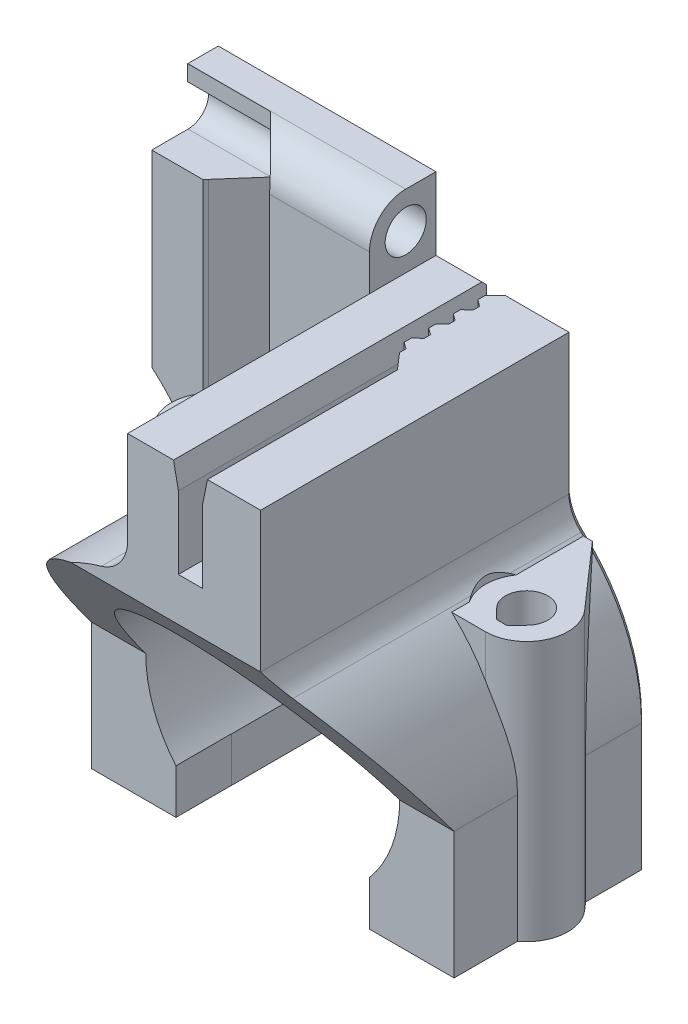
SolidWorks part; units mm, degrees
material "Custom Plastic"
ref_plane "Front Plane" through (0, 0, 0) normal (0, 0, 1) x (1, 0, 0)
ref_plane "Top Plane" through (0, 0, 0) normal (0, 1, 0) x (1, 0, 0)
ref_plane "Right Plane" through (0, 0, 0) normal (1, 0, 0) x (0, 0, -1)
sketch "Sketch1" plane through (0, 0, 0) normal (0, 0, 1) x (1, 0, 0)
  line L0 (-23.622, -10.5) -> (30.4823, -10.5) construction
  line L1 (-23.622, -16.5) -> (30.4823, -16.5) construction
  line L2 (8, -6.8007) -> (8, -10.5)
  line L3 (8, -10.5) -> (15, -10.5)
  line L4 (-15, -10.5) -> (-8, -10.5)
  line L5 (-8, -6.8007) -> (-8, -10.5)
  line L6 (15, 0) -> (15, -10.5)
  line L7 (-2, 25) -> (9, 25)
  line L9 (9, 25) -> (9, 13.4164)
  line L10 (-2, 25) -> (-2, 17.2916)
  line L12 (-15, -10.5) -> (-15, 0)
  arc A0 (-4.1667, 14.4097) -> (-2, 17.2916) centre (-5, 17.2916) ccw
  arc A1 (15, 0) -> (10, 11.1803) centre (0, 0) ccw
  arc A2 (10, 11.1803) -> (9, 13.4164) centre (12, 13.4164) cw
  arc A4 (8, -6.8007) -> (-8, -6.8007) centre (0, 0) ccw
  arc A5 (-4.1667, 14.4097) -> (-15, 0) centre (0, 0) ccw
  dimension "D1" = 16
  dimension "D4" = 25
  dimension "D5" = 2
  dimension "D6" = 21
  dimension "D7" = 4.5
  dimension "D3" = 3
  dimension "D8" = 3
  dimension "D9" = 9
  dimension "D2" = 6
extrude "Boss-Extrude1" add sketch "Sketch1" along normal blind 26
sketch "Sketch4" plane through (0, -10.5, 0) normal (0, -1, 0) x (1, 0, 0)
  line L0 (10.939, 0.5) -> (7.9931, 0.5)
  line L3 (13, 11.4) -> (7.9931, 11.4)
  line L4 (7.9931, 11.4) -> (7.9931, 0.5)
  line L5 (10.939, 0.5) -> (15.5548, 5.7566)
  arc A1 (15.5548, 5.7566) -> (13, 11.4) centre (13, 8) ccw
  dimension "D1" = 3.4
  dimension "D2" = 13
  dimension "D4" = 8
extrude "Boss-Extrude2" add sketch "Sketch4" against normal blind 21.5
sketch "Sketch2" plane through (0, -10.5, 0) normal (0, -1, 0) x (1, 0, 0)
  line L0 (13, 16) -> (13, 0) construction
  circle A0 centre (13, 8) radius 1.75
  arc A3 (15.5548, 5.7566) -> (15, 10.7495) centre (13, 8) ccw construction
  dimension "D1" = 3.5
extrude "Cut-Extrude1" cut sketch "Sketch2" against normal through all
mirror "Mirror1" about plane through (0, 0, 0) normal (1, 0, 0) of "Boss-Extrude2", "Cut-Extrude1"
sketch "Sketch5" plane through (0, -10.5, 0) normal (0, -1, 0) x (1, 0, 0)
  line L0 (-13, 8) -> (-11.7626, 9.2374)
  line L1 (-11.7626, 9.2374) -> (-12.5951, 10.07)
  line L2 (-12.5951, 10.07) -> (-13.4049, 10.07)
  line L3 (-13.4049, 10.07) -> (-14.2374, 9.2374)
  line L4 (-14.2374, 9.2374) -> (-13, 8)
  line L5 (13, 8) -> (14.2374, 9.2374)
  line L6 (14.2374, 9.2374) -> (13.4049, 10.07)
  line L7 (12.5951, 10.07) -> (11.7626, 9.2374)
  line L8 (11.7626, 9.2374) -> (13, 8)
  line L9 (12.5951, 10.07) -> (13.4049, 10.07)
  circle A0 centre (-13, 8) radius 1.75 construction
  circle A1 centre (13, 8) radius 1.75 construction
  point P0 (-13, 9.75)
  point P4 (13, 9.75)
  dimension "D1" = 0.32
  dimension "D2" = 0.32
extrude "Cut-Extrude3" cut sketch "Sketch5" against normal through all
sketch "Sketch7" plane through (0, 25, 0) normal (0, 1, 0) x (1, 0, 0)
  line L0 (3.2, -3.116) -> (3.2, -10.7303) construction
  line L1 (3.45, -2.334) -> (2.9, -1.934)
  line L2 (2.9, -1.934) -> (2.9, -1.334)
  line L19 (4.2, -9.8281) -> (4.2, -26)
  line L22 (3.45, -8.962) -> (4.2, -9.8281)
  line L23 (2.9, -1.334) -> (4.2, 0)
  line L24 (3.45, -8.43) -> (3.45, -8.962)
  line L25 (3.45, -6.398) -> (3.45, -6.93)
  line L26 (3.45, -4.366) -> (3.45, -4.898)
  line L27 (2.9, -8.03) -> (3.45, -8.43)
  line L28 (2.9, -7.43) -> (2.9, -8.03)
  line L29 (3.45, -6.93) -> (2.9, -7.43)
  line L30 (2.9, -5.998) -> (3.45, -6.398)
  line L31 (2.9, -5.398) -> (2.9, -5.998)
  line L32 (3.45, -4.898) -> (2.9, -5.398)
  line L33 (2.9, -3.966) -> (3.45, -4.366)
  line L34 (2.9, -3.366) -> (2.9, -3.966)
  line L35 (3.45, -2.866) -> (2.9, -3.366)
  line L36 (2.2, 0) -> (2.2, -26)
  line L37 (4.2, -26) -> (2.2, -26)
  line L38 (3.45, -2.334) -> (3.45, -2.866)
  line L39 (4.2, 0) -> (2.2, 0)
  point P0 (3.2, -3.116)
  dimension "D1" = 0.6
  dimension "D2" = 0.55
  dimension "D3" = 2.032
  dimension "D4" = 1.25
  dimension "D5" = 2
  dimension "D8" = 3.2
extrude "Cut-Extrude4" cut sketch "Sketch7" against normal blind 8
sketch "Sketch13" plane through (0, 0, 0) normal (0, 0, -1) x (-1, 0, 0)
  line L0 (2, 17.2916) -> (2, 31)
  line L1 (2, 31) -> (20, 31)
  line L2 (20, 31) -> (20, 10.7393)
  line L3 (-2.2, 25) -> (2, 25) construction
  line L4 (15, 0) -> (15, -10.5) construction
  arc A0 (2, 17.2916) -> (4.1667, 14.4097) centre (5, 17.2916) ccw
  arc A1 (15, 0) -> (4.1667, 14.4097) centre (0, 0) ccw
  arc A2 (20, 10.7393) -> (15, 0) centre (29.0333, 0) ccw
  dimension "D1" = 6
  dimension "D2" = 5
extrude "Boss-Extrude4" add sketch "Sketch13" against normal blind 6
sketch "Sketch9" plane through (0, 0, 0) normal (1, 0, 0) x (0, 0, -1)
  line L0 (-26, 13.4164) -> (-16, 0)
  line L1 (-26, 0) -> (-10.7495, 0) construction
  line L2 (-16, 0) -> (-16, -10.5)
  line L3 (-26, -10.5) -> (-10.7495, -10.5) construction
  line L4 (-16, -10.5) -> (-26, -10.5)
  line L5 (-26, -10.5) -> (-26, 13.4164)
  dimension "D1" = 16
extrude "Cut-Extrude5" cut sketch "Sketch9" against normal through all and the other way through all
sketch "Sketch10" plane through (0, 11, 0) normal (0, 1, 0) x (1, 0, 0)
  line L0 (-10.5958, -10.4042) -> (-16.4, -16.2083)
  line L1 (16.4, -8) -> (16.4, -16.2083)
  line L2 (-10.5958, -5.5958) -> (-13.1611, -3.0306)
  line L3 (15, 29.0402) -> (-15, -5.1247) construction
  line L4 (-13.1611, -3.0306) -> (-15.5548, -5.7566)
  line L5 (0, 0) -> (0, -28.6456) construction
  line L6 (13.1611, -3.0306) -> (15.5548, -5.7566)
  line L7 (10.5958, -5.5958) -> (13.1611, -3.0306)
  line L8 (10.5958, -10.4042) -> (16.4, -16.2083)
  line L10 (-16.4, -8) -> (-16.4, -16.2083)
  arc A0 (10.5958, -10.4042) -> (10.5958, -5.5958) centre (13, -8) cw
  arc A1 (-15.5548, -5.7566) -> (-16.4, -8) centre (-13, -8) ccw
  arc A2 (15.5548, -5.7566) -> (16.4, -8) centre (13, -8) cw
  arc A3 (-10.5958, -10.4042) -> (-10.5958, -5.5958) centre (-13, -8) ccw
extrude "Cut-Extrude6" cut sketch "Sketch10" along normal through all
chamfer "Chamfer1" distance 0.4 distance2 2 2 edges at (2.2, 25, 13) (4.2, 25, 17.914) first distance on face at (-0.32, 25, 11.6) first distance on face at (3.8762, 25, 6.8795)
fillet "Fillet1" radius 3 1 edges at (-6.1252, 31, 6)
sketch "Sketch14" plane through (-2, 0, 0) normal (1, 0, 0) x (0, 0, -1)
  circle A0 centre (-3, 28) radius 1.7
  dimension "D1" = 3.4
extrude "Cut-Extrude8" cut sketch "Sketch14" against normal through all
sketch "Sketch15" plane through (-20, 0, 0) normal (-1, 0, 0) x (0, 0, 1)
  line L2 (3, 26.3) -> (6, 26.3)
  line L3 (6, 10.7393) -> (6, 28) construction
  line L4 (6, 26.3) -> (6, 31)
  line L5 (6, 31) -> (3.0306, 31)
  line L6 (3.0306, 29.6997) -> (3.0306, 31)
  arc A0 (3.0306, 29.6997) -> (3, 26.3) centre (3, 28) ccw
extrude "Cut-Extrude9" cut sketch "Sketch15" against normal up to vertex (6.8389 mm away) up to point (-13.1611, 26.3003, 3.0306)
chamfer "Chamfer2" distance 0.5 angle 45 18 edges at (6.6, 25, 0) (9, 19.2082, 0) (9.2614, 12.1917, 0) (13.6931, 6.1237, 0) (15, -5.25, 0) (11.5, -10.5, 0) (8, -8.6504, 0) (0, 10.5, 0) (-8, -8.6504, 0) (-11.5, -10.5, 0) (-15, -5.25, 0) (-16.3113, 5.9231, 0) (-20, 20.8697, 0) (-11, 31, 0) (-2, 28, 0) (3.2, 17, 0) (2.2, 20, 0) (-0.1, 25, 0)
sketch "Sketch16" plane through (0, 0, 0) normal (0, 0, 1) x (1, 0, 0)
  circle A0 centre (0, 0) radius 10.5
  arc A1 (10.5, 0) -> (-10.5, 0) centre (0, 0) ccw construction
extrude "Cut-Extrude11" cut sketch "Sketch16" along normal through all
